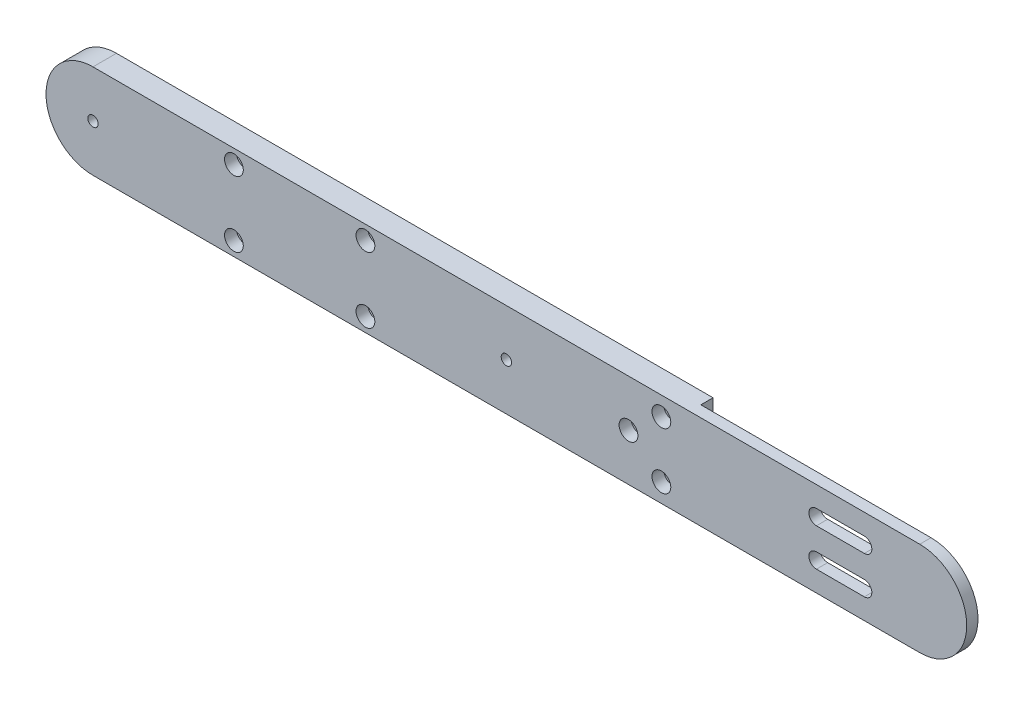
SolidWorks part; units mm, degrees
ref_plane "前视基准面" through (0, 0, 0) normal (0, 0, 1) x (1, 0, 0)
ref_plane "上视基准面" through (0, 0, 0) normal (0, 1, 0) x (1, 0, 0)
ref_plane "右视基准面" through (0, 0, 0) normal (1, 0, 0) x (0, 0, -1)
other "Configuration Table"
sketch "草图1" plane through (0, 0, 0) normal (0, 0, 1) x (1, 0, 0)
  line L0 (0, 0) -> (176, 0) construction
  line L5 (0, 10) -> (176, 10)
  line L6 (0, 10) -> (0, -10)
  line L7 (0, -10) -> (176, -10)
  line L8 (176, 10) -> (176, -10)
  circle A2 centre (0, 0) radius 10
  circle A5 centre (88, 0) radius 2.55
  circle A8 centre (88, 0) radius 1.1
  circle A9 centre (0, 0) radius 2.55
  circle A10 centre (0, 0) radius 1.1
  circle A11 centre (176, 0) radius 10
  dimension "D1" = 20
  dimension "D2" = 176
  dimension "D4" = 2.2
  dimension "D5" = 5.1
  dimension "D3" = 176
extrude "凸台-拉伸1" add sketch "草图1" along normal blind 5 contours A2 | L7 L8 L5 L6 | A11
extrude "切除-拉伸2" cut sketch "草图1<3>" along normal through all contours A10 | A8
sketch "草图1<3>" plane through (0, 0, 0) normal (0, 0, 1) x (1, 0, 0) same geometry as "草图1"
extrude "切除-拉伸3" cut sketch "草图1<4>" along normal blind 2.6 contours A5 | A9
sketch "草图1<4>" plane through (0, 0, 0) normal (0, 0, 1) x (1, 0, 0) same geometry as "草图1"
sketch "草图2" plane through (0, 0, 0) normal (0, 0, -1) x (-1, 0, 0)
  line L0 (0, -10) -> (-176, -10) construction
  line L1 (0, 10) -> (-176, 10) construction
  line L2 (-121, 6) -> (-121, -6) construction
  circle A0 centre (-121, -6) radius 1.25
  circle A1 centre (-121, 6) radius 1.25
  circle A2 centre (-121, -6) radius 2
  circle A3 centre (-121, 6) radius 2
  circle A4 centre (-88, 0) radius 1.1 construction
  circle A5 centre (-114, 0) radius 2
  circle A6 centre (-114, 0) radius 1.25
  circle A7 centre (-58, 7) radius 1.25
  circle A9 centre (-58, 7) radius 2
  circle A10 centre (-30, 7) radius 2
  circle A11 centre (-30, 7) radius 1.25
  circle A12 centre (-58, -7) radius 2
  circle A13 centre (-58, -7) radius 1.25
  circle A14 centre (-30, -7) radius 1.25
  circle A15 centre (-30, -7) radius 2
  point P16 (-121, 0)
  point P29 (0, 0)
  point P30 (0, 0)
  point P31 (0, 0)
  point P32 (0, 0)
  point P34 (0, 0)
  point P35 (0, 0)
  point P36 (0, 0)
  point P37 (0, 0)
  dimension "D1" = 4
  dimension "D2" = 2.5
  dimension "D3" = 33
  dimension "D4" = 4
  dimension "D5" = 4
  dimension "D6" = 7
  dimension "D7" = 30
  dimension "D8" = 30
  dimension "D9" = 3
  dimension "D10" = 3
extrude "切除-拉伸4" cut sketch "草图2" against normal through all contours A1 | A0 | A6 | A13 | A14 | A11 | A7
extrude "切除-拉伸5" cut sketch "草图2<3>" along normal offset from surface (2.5 mm away) 2.5 from surface contours A3 | A2 | A5 | A9 | A10 | A15 | A12 up to face at (56.75, 7, 0) starting at face at (56.75, 7, 5)
sketch "草图2<3>" plane through (0, 0, 0) normal (0, 0, -1) x (-1, 0, 0) same geometry as "草图2"
sketch "草图3" plane through (0, 10, 0) normal (0, 1, 0) x (1, 0, 0)
  line L0 (0, 0) -> (176, 0) construction
  line L1 (127, 0) -> (186, 0)
  line L2 (127, 0) -> (127, -2.6)
  line L3 (127, -2.6) -> (186, -2.6)
  line L4 (186, 0) -> (186, -2.6)
  dimension "D1" = 59
  dimension "D2" = 2.6
extrude "切除-拉伸6" cut sketch "草图3" against normal through all
sketch "草图4" plane through (0, 0, 5) normal (0, 0, 1) x (1, 0, 0)
  line L0 (164.2, -2.4) -> (154, -2.4)
  line L5 (164.2, -2.4) -> (164.2, -5.6)
  line L6 (164.2, -5.6) -> (154, -5.6)
  line L7 (154, -2.4) -> (154, -5.6)
  line L8 (164.2, 5.6) -> (154, 5.6)
  line L9 (164.2, 5.6) -> (164.2, 2.4)
  line L10 (164.2, 2.4) -> (154, 2.4)
  line L11 (154, 5.6) -> (154, 2.4)
  line L12 (154, 4) -> (154, -4)
  line L13 (186, 0) -> (154, 0)
  circle A3 centre (164.2, -4) radius 1.6
  circle A4 centre (154, -4) radius 1.6
  circle A5 centre (164.2, 4) radius 1.6
  circle A6 centre (154, 4) radius 1.6
  arc A7 (176, -10) -> (176, 10) centre (176, 0) ccw construction
  dimension "D1" = 10.2
  dimension "D3" = 3.2
  dimension "D4" = 3.2
  dimension "D2" = 8
  dimension "D5" = 32
extrude "切除-拉伸7" cut sketch "草图4" against normal through all contours A6 | L10 L11 L8 L9 | A5 | L6 L7 L0 L5 | A4 | A3
